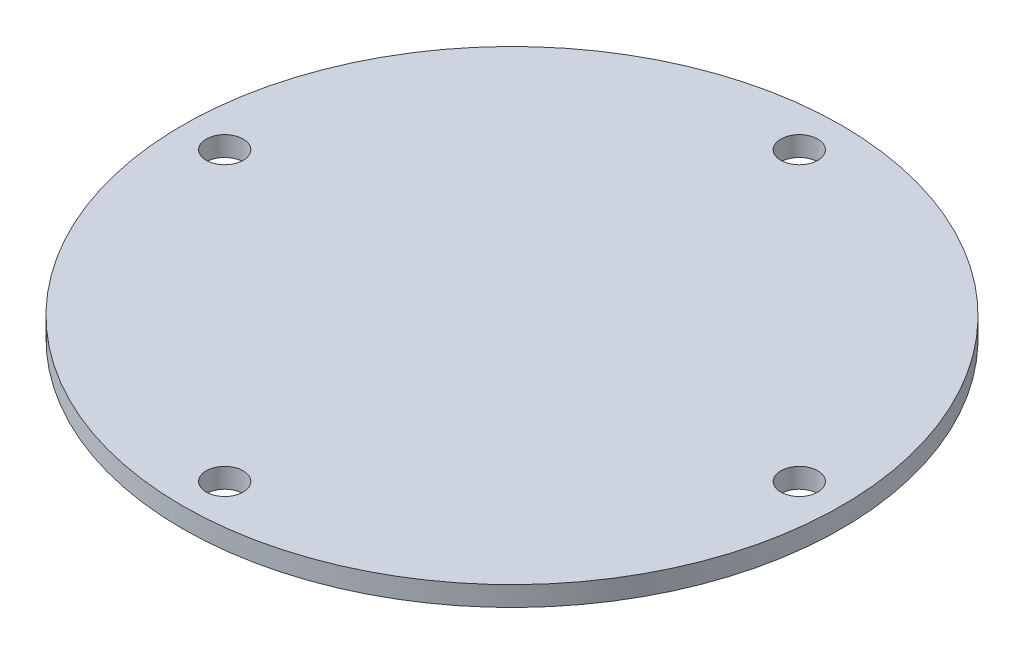
SolidWorks part; units mm, degrees
ref_plane "Front Plane" through (0, 0, 0) normal (0, 0, 1) x (1, 0, 0)
ref_plane "Top Plane" through (0, 0, 0) normal (0, 1, 0) x (1, 0, 0)
ref_plane "Right Plane" through (0, 0, 0) normal (1, 0, 0) x (0, 0, -1)
sketch "Sketch1" plane through (0, 0, 0) normal (0, 1, 0) x (1, 0, 0)
  circle A0 centre (0, 0) radius 62.4
  dimension "PCBdiam" = 124.8
extrude "Boss-Extrude1" add sketch "Sketch1" along normal blind 3.75
hole_wizard "M6 Clearance Hole1" positions "Sketch2" profile "Sketch4" hole size "M6" standard "ANSI Metric" end condition through all
sketch "Sketch2" plane through (0, 3.75, 0) normal (0, 1, 0) x (1, 0, 0)
  line L0 (0, 0) -> (0, 29.5662) construction
  circle A0 centre (0, 0) radius 62.4 construction
  point P7 (-54.4, 0)
  dimension "holeRadius" = 54.4
sketch "Sketch4" plane through (-54.4, 3.75, 0) normal (1, 0, 0) x (0, 0, 1)
  line L0 (0, 0) -> (0, 3.75)
  line L1 (0, 3.75) -> (3.5, 3.75)
  line L2 (3.5, 3.75) -> (3.5, 0)
  line L5 (3.5, 0) -> (0, 0)
  line L11 (0, -6.35) -> (0, 107.95) construction
  dimension "Thru Hole Dia." = 7
  dimension "Thru Hole Depth" = 3.75
pattern_circular "CirPattern1" count 4 over 360 about axis through (0, 3.75, 0) along (0, -1, 0) of "M6 Clearance Hole1"
